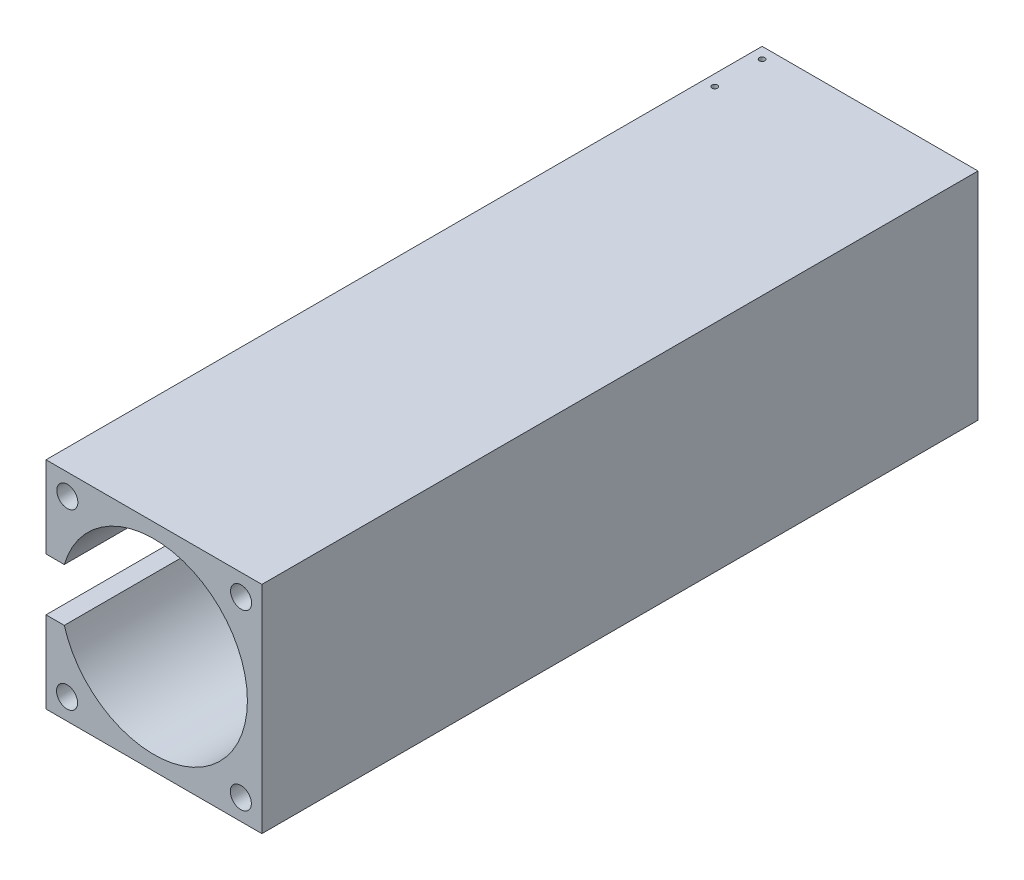
SolidWorks part; units mm, degrees
ref_plane "前基準面" through (0, 0, 0) normal (0, 0, 1) x (1, 0, 0)
ref_plane "上基準面" through (0, 0, 0) normal (0, 1, 0) x (1, 0, 0)
ref_plane "右基準面" through (0, 0, 0) normal (1, 0, 0) x (0, 0, -1)
ref_axis "基準軸1" through (0, -55, 0) along (0, 1, 0)
ref_axis "基準軸2" through (-88.99, 0, 0) along (1, 0, 0)
ref_axis "基準軸3" through (0, 0, 55) along (0, 0, -1)
sketch "草圖1" plane through (0, 0, 0) normal (0, 0, 1) x (1, 0, 0)
  line L0 (0, -55) -> (0, 55) construction
  line L1 (-41, -41) -> (41, -41)
  line L2 (-41, -41) -> (-41, 41)
  line L3 (-41, 41) -> (41, 41)
  line L4 (41, -41) -> (41, 41)
  line L5 (55, 0) -> (-55, 0) construction
  circle A0 centre (0, 0) radius 35.5
  point P7 (0, -41)
  point P10 (41, 0)
  dimension "D1" = 71
  dimension "D2" = 82
  dimension "D3" = 82
extrude "填料-伸長1" add sketch "草圖1" along normal blind 245
sketch "草圖2" plane through (0, 0, 0) normal (0, 0, -1) x (-1, 0, 0)
  line L1 (-41, 41) -> (41, 41)
  line L2 (-41, 41) -> (-41, -41)
  line L3 (-41, -41) -> (41, -41)
  line L4 (41, 41) -> (41, -41)
extrude "填料-伸長2" add sketch "草圖2" along normal blind 27
ref_plane "平面1" through (0, 0, -13.5) normal (0, 0, -1) x (-1, 0, 0)
sketch "草圖3" plane through (0, 0, 245) normal (0, 0, 1) x (1, 0, 0)
  line L0 (-41, 41) -> (-41, -41) construction
  line L1 (-41, 10) -> (-33, 10)
  line L2 (-41, 10) -> (-41, -10)
  line L3 (-41, -10) -> (-33, -10)
  line L4 (-33, 10) -> (-33, -10)
  line L6 (55, 0) -> (-55, 0) construction
  point P6 (-33, 0)
  dimension "D1" = 8
  dimension "D2" = 20
extrude "除料-伸長1" cut sketch "草圖3" against normal up to surface (245 mm away) up to face at (35.5, 0, 0)
sketch "草圖4" plane through (0, 0, 245) normal (0, 0, 1) x (1, 0, 0)
  line L1 (41, 41) -> (-41, 41) construction
  line L2 (-41, 41) -> (-41, 10) construction
  line L3 (-41, -41) -> (41, -41) construction
  line L4 (-41, -10) -> (-41, -41) construction
  circle A0 centre (-32.9, 33) radius 4
  circle A1 centre (33.1, 32.9) radius 4
  circle A2 centre (33, -33.1) radius 4
  circle A3 centre (-33, -33) radius 4
  point P15 (0.05, -0.05)
  dimension "D1" = 8
  dimension "D5" = 8
  dimension "D2" = 8
  dimension "D3" = 8.1
  dimension "D6" = 8
  dimension "D4" = 4
extrude "除料-伸長2" cut sketch "草圖4" against normal blind 20
fillet "圓角2" radius 3 1 edges at (-28.9, 33, 225)
fillet "圓角3" radius 3 1 edges at (37.1, 32.9, 225)
fillet "圓角4" radius 3 1 edges at (-29, -33, 225)
fillet "圓角5" radius 3 1 edges at (37, -33.1, 225)
sketch "草圖5" plane through (0, 41, 0) normal (0, 1, 0) x (1, 0, 0)
  line L0 (-41, -245) -> (-41, 27) construction
  line L4 (-41, 27) -> (41, 27) construction
  circle A2 centre (-36.75, 22.75) radius 1.05
  circle A3 centre (-36.75, 4.75) radius 1.05
  point P8 (-36.7138, 25.7547)
  dimension "D1" = 18
  dimension "D2" = 2.1
  dimension "D3" = 2.1
  dimension "D4" = 4.25
  dimension "D5" = 4.25
  dimension "D6" = 4.25
extrude "除料-伸長3" cut sketch "草圖5" against normal blind 10
ref_plane "平面2" through (0, 35, 0) normal (0, 1, 0) x (1, 0, 0)
sketch "草圖6" plane through (0, 35, 0) normal (0, 1, 0) x (1, 0, 0)
  circle A0 centre (-36.75, 22.75) radius 1.05
  circle A1 centre (-36.75, 4.75) radius 1.05
  dimension "D1" = 2.1
  dimension "D2" = 2.1
extrude "填料-伸長3" add sketch "草圖6" along normal blind 0.2
